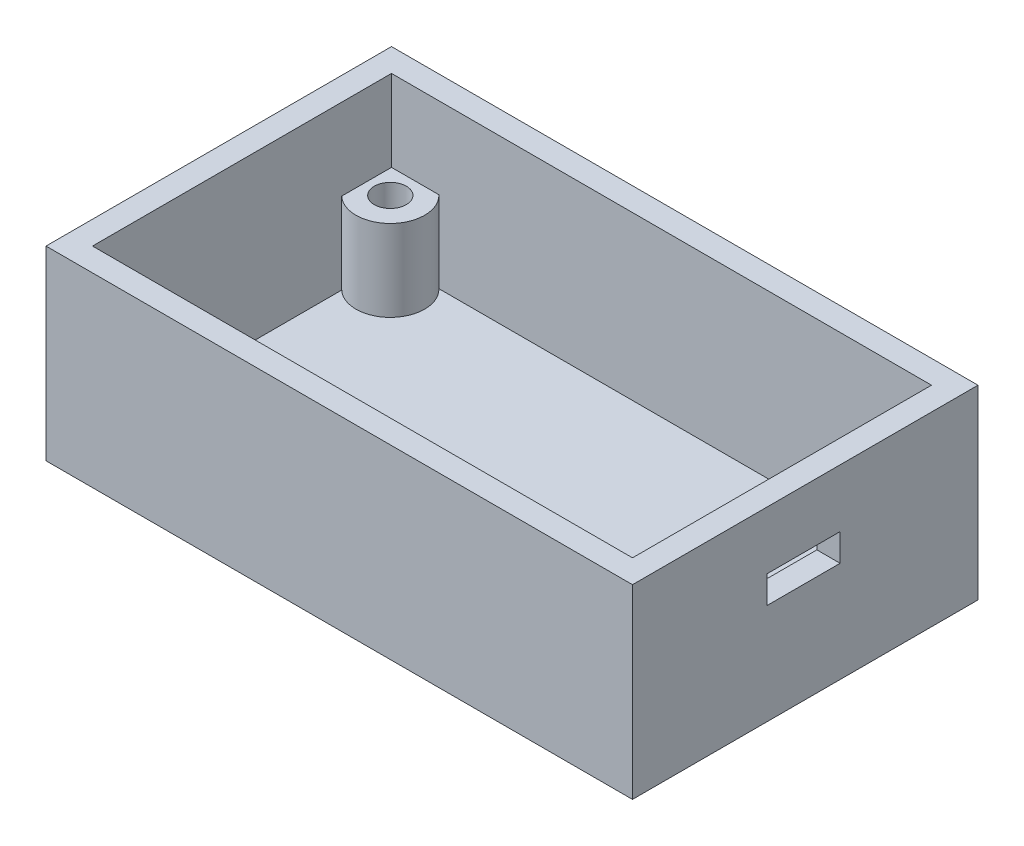
SolidWorks part; units mm, degrees
ref_plane "Front Plane" through (0, 0, 0) normal (0, 0, 1) x (1, 0, 0)
ref_plane "Top Plane" through (0, 0, 0) normal (0, 1, 0) x (1, 0, 0)
ref_plane "Right Plane" through (0, 0, 0) normal (1, 0, 0) x (0, 0, -1)
sketch "Sketch1" plane through (0, 0, 0) normal (0, 1, 0) x (1, 0, 0)
  line L0 (0, 0) -> (-29.5, 0) construction
  line L1 (-29.5, -16.3345) -> (29.5, -16.3345)
  line L2 (-29.5, -16.3345) -> (-29.5, 16.3345)
  line L3 (-29.5, 16.3345) -> (29.5, 16.3345)
  line L4 (29.5, -16.3345) -> (29.5, 16.3345)
  line L5 (-29.5, -16.3345) -> (29.5, 16.3345) construction
  line L6 (-29.5, 16.3345) -> (29.5, -16.3345) construction
  line L7 (0, 0) -> (0, 16.3345) construction
  line L8 (-32.04, 18.8745) -> (32.04, 18.8745)
  line L9 (32.04, -18.8745) -> (32.04, 18.8745)
  line L10 (-32.04, -18.8745) -> (32.04, -18.8745)
  line L11 (-32.04, -18.8745) -> (-32.04, 18.8745)
  circle A0 centre (-27.43, -14.2658) radius 1.75
  circle A1 centre (-27.43, 14.2658) radius 1.75
  circle A2 centre (27.43, -14.2658) radius 1.75
  circle A3 centre (27.43, 14.2658) radius 1.75
  point P0 (0, 0)
  dimension "D3" = 3.5
  dimension "D5" = 2.07
  dimension "D1" = 32.669
  dimension "D2" = 59
  dimension "D4" = 2.0687
  dimension "D6" = 2.54
extrude "Boss-Extrude1" add sketch "Sketch1" against normal blind 20.32 contours L10 L9 L8 L11
extrude "Cut-Extrude1" cut sketch "Sketch1<6>" against normal blind 17.78 contours L2 L3 L4 L1
sketch "Sketch1<6>" plane through (0, 0, 0) normal (0, 1, 0) x (1, 0, 0) same geometry as "Sketch1"
sketch "Sketch4" plane through (0, -17.78, 0) normal (0, 1, 0) x (1, 0, 0)
  line L0 (-29.5, 16.3345) -> (-24.3228, 16.3345)
  line L1 (-29.5, -16.3345) -> (-29.5, 16.3345) construction
  line L2 (0, 0) -> (0, 16.3345) construction
  line L4 (-29.5, 10.8971) -> (-29.5, 16.3345)
  line L5 (-29.5, 16.3345) -> (29.5, -16.3345) construction
  line L6 (0, 0) -> (-29.5, 0) construction
  line L7 (29.5, 10.8971) -> (29.5, 16.3345)
  line L8 (29.5, 16.3345) -> (24.3228, 16.3345)
  line L9 (29.5, -10.8971) -> (29.5, -16.3345)
  line L10 (29.5, -16.3345) -> (24.3228, -16.3345)
  line L11 (-29.5, -10.8971) -> (-29.5, -16.3345)
  line L12 (-29.5, -16.3345) -> (-24.3228, -16.3345)
  line L13 (-29.5, 16.3345) -> (29.5, 16.3345) construction
  circle A30 centre (-26.9114, 13.6158) radius 1.75
  circle A31 centre (26.9114, 13.6158) radius 1.75
  circle A32 centre (26.9114, -13.6158) radius 1.75
  circle A33 centre (-26.9114, -13.6158) radius 1.75
  arc A34 (-29.5, 10.8971) -> (-24.3228, 16.3345) centre (-26.9114, 13.6158) ccw
  arc A36 (29.5, 10.8971) -> (24.3228, 16.3345) centre (26.9114, 13.6158) cw
  arc A37 (29.5, -10.8971) -> (24.3228, -16.3345) centre (26.9114, -13.6158) ccw
  arc A38 (-29.5, -10.8971) -> (-24.3228, -16.3345) centre (-26.9114, -13.6158) cw
  point P25 (-25.3531, 17.031)
  point P26 (-24.2788, 16.3345)
extrude "Boss-Extrude2" add sketch "Sketch4" along normal blind 8.89
sketch "Sketch6" plane through (32.04, 0, 0) normal (1, 0, 0) x (0, 0, -1)
  line L2 (-18.8745, -20.32) -> (18.8745, -20.32) construction
  line L3 (-18.8745, -9.32) -> (18.8745, -9.32) construction
  line L6 (-18.8745, -20.32) -> (-18.8745, 0) construction
  line L11 (18.8745, -20.32) -> (18.8745, 0) construction
  line L13 (-4.19, -6.32) -> (3.81, -6.32)
  line L14 (-4.19, -6.32) -> (-4.19, -9.32)
  line L15 (-4.19, -9.32) -> (3.81, -9.32)
  line L16 (3.81, -6.32) -> (3.81, -9.32)
  line L17 (-4.19, -6.32) -> (3.81, -9.32) construction
  line L18 (-4.19, -9.32) -> (3.81, -6.32) construction
  point P12 (-0.19, -7.82)
  dimension "D1" = 11
  dimension "D2" = 3
  dimension "D3" = 8
extrude "Cut-Extrude2" cut sketch "Sketch6" against normal blind 8.89
